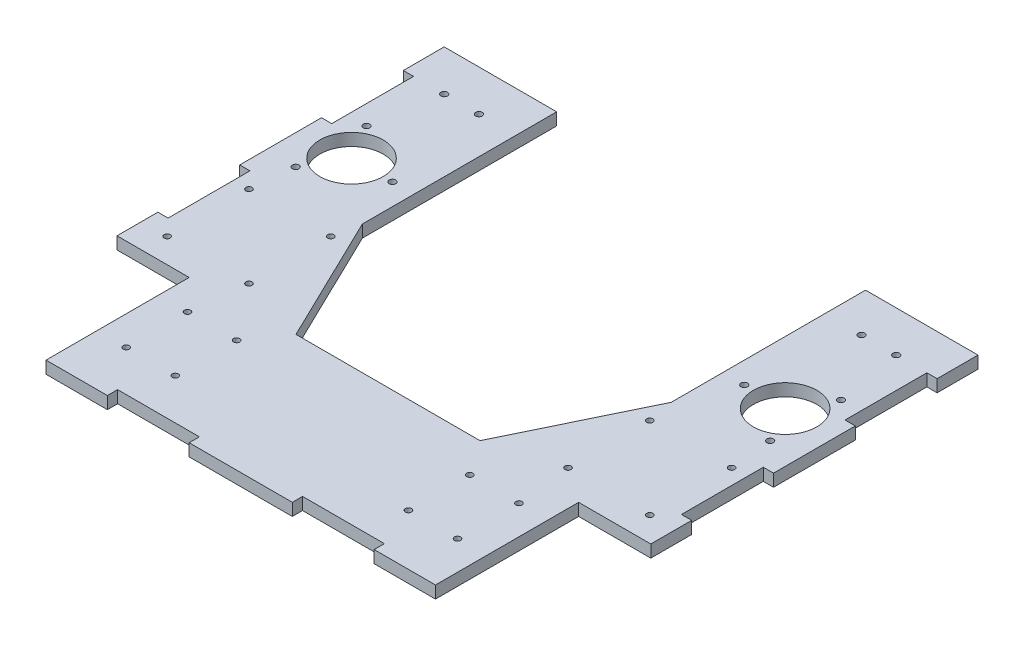
SolidWorks part; units mm, degrees
ref_plane "Front Plane" through (0, 0, 0) normal (0, 0, 1) x (1, 0, 0)
ref_plane "Top Plane" through (0, 0, 0) normal (0, 1, 0) x (1, 0, 0)
ref_plane "Right Plane" through (0, 0, 0) normal (1, 0, 0) x (0, 0, -1)
sketch "Sketch3" plane through (0, 0, 0) normal (0, 1, 0) x (1, 0, 0)
  line L0 (-85.1329, 76.7277) -> (-85.1329, -123.2723)
  line L1 (-85.1329, 76.7277) -> (-30.1329, 76.7277)
  line L2 (-30.1329, 76.7277) -> (-30.1329, 11.7277)
  line L3 (-30.1329, 11.7277) -> (0.3794, -51.2723)
  line L4 (0.3794, -51.2723) -> (90.3794, -51.2723)
  line L5 (-85.1329, -123.2723) -> (175.8917, -123.2723)
  line L6 (45.3794, 120.3098) -> (45.3794, -136.4066) construction
  line L7 (120.8917, 11.7277) -> (90.3794, -51.2723)
  line L8 (120.8917, 76.7277) -> (120.8917, 11.7277)
  line L9 (175.8917, 76.7277) -> (120.8917, 76.7277)
  line L10 (175.8917, 76.7277) -> (175.8917, -123.2723)
  point P11 (45.3794, -123.2723)
  point P12 (45.3794, -51.2723)
  dimension "D1" = 200
  dimension "D2" = 55
  dimension "D3" = 65
  dimension "D4" = 45
  dimension "D5" = 70
  dimension "D6" = 72
  dimension "D7" = 55
  dimension "D8" = 200
  dimension "D9" = 261.0246
  dimension "D10" = 151.0246
extrude "Boss-Extrude1" add sketch "Sketch3" along normal blind 6
sketch "Sketch4" plane through (0, 6, 0) normal (0, 1, 0) x (1, 0, 0)
  line L0 (-54.8456, -88.8518) -> (-54.8456, -98.9429) construction
  line L1 (-85.1329, -123.2723) -> (-49.8456, -123.2723)
  line L2 (-85.1329, -123.2723) -> (-85.1329, -53.2723)
  line L3 (-85.1329, -53.2723) -> (-49.8456, -53.2723)
  line L4 (-49.8456, -123.2723) -> (-49.8456, -53.2723)
  line L5 (45.3794, -51.2723) -> (45.3794, 91.9306) construction
  line L6 (90.3794, -51.2723) -> (0.3794, -51.2723) construction
  line L7 (140.6044, -123.2723) -> (140.6044, -53.2723)
  line L8 (175.8917, -53.2723) -> (140.6044, -53.2723)
  line M8 (-85.1329, -123.2723) -> (175.8917, -123.2723)
  line M9 (175.8917, -123.2723) -> (175.8917, 76.7277)
  dimension "D1" = 5
  dimension "D2" = 70
extrude "Cut-Extrude1" cut sketch "Sketch4" against normal blind 10 contours L8 L7 M9 M8 | L3 L4 L1 L2 region at (158.248, 6, 88.2723)
sketch "Sketch8" plane through (0, 0, -76.7277) normal (0, 0, -1) x (-1, 0, 0)
  line L1 (-175.8917, 6) -> (-120.8917, 6)
  line L2 (-175.8917, 6) -> (-175.8917, 0)
  line L3 (-175.8917, 0) -> (-120.8917, 0)
  line L4 (-120.8917, 6) -> (-120.8917, 0)
  line L5 (30.1329, 6) -> (85.1329, 6)
  line L6 (30.1329, 6) -> (30.1329, 0)
  line L7 (30.1329, 0) -> (85.1329, 0)
  line L8 (85.1329, 6) -> (85.1329, 0)
extrude "Boss-Extrude2" add sketch "Sketch8" along normal blind 30
sketch "Sketch10" plane through (0, 6, 0) normal (0, 1, 0) x (1, 0, 0)
  line L0 (-85.1329, 106.7277) -> (-85.1329, -53.2723) construction
  line L1 (-85.1329, 86.7277) -> (-80.1329, 86.7277)
  line L2 (-85.1329, 86.7277) -> (-85.1329, 46.7277)
  line L3 (-85.1329, 46.7277) -> (-80.1329, 46.7277)
  line L4 (-80.1329, 86.7277) -> (-80.1329, 46.7277)
  line L6 (-85.1329, 6.7277) -> (-80.1329, 6.7277)
  line L7 (-85.1329, 6.7277) -> (-85.1329, -33.2723)
  line L8 (-85.1329, -33.2723) -> (-80.1329, -33.2723)
  line L9 (-80.1329, 6.7277) -> (-80.1329, -33.2723)
  line L10 (-85.1329, 106.7277) -> (-30.1329, 106.7277) construction
  line L11 (-85.1329, -53.2723) -> (-49.8456, -53.2723) construction
  line L12 (45.3794, -51.2723) -> (45.3794, 130.7812) construction
  line L13 (90.3794, -51.2723) -> (0.3794, -51.2723) construction
  line L14 (170.8917, 6.7277) -> (170.8917, -33.2723)
  line L15 (175.8917, -33.2723) -> (170.8917, -33.2723)
  line L16 (175.8917, 6.7277) -> (175.8917, -33.2723)
  line L17 (175.8917, 6.7277) -> (170.8917, 6.7277)
  line L18 (170.8917, 86.7277) -> (170.8917, 46.7277)
  line L19 (175.8917, 46.7277) -> (170.8917, 46.7277)
  line L20 (175.8917, 86.7277) -> (175.8917, 46.7277)
  line L21 (175.8917, 86.7277) -> (170.8917, 86.7277)
  line L22 (-49.8456, -123.2723) -> (140.6044, -123.2723) construction
  line L23 (-19.8456, -123.2723) -> (20.1544, -123.2723)
  line L24 (-19.8456, -123.2723) -> (-19.8456, -118.2723)
  line L25 (-19.8456, -118.2723) -> (20.1544, -118.2723)
  line L26 (20.1544, -123.2723) -> (20.1544, -118.2723)
  line L27 (-49.8456, -123.2723) -> (-49.8456, -53.2723) construction
  line L28 (70.6044, -123.2723) -> (110.6044, -123.2723)
  line L29 (70.6044, -123.2723) -> (70.6044, -118.2723)
  line L30 (70.6044, -118.2723) -> (110.6044, -118.2723)
  line L31 (110.6044, -123.2723) -> (110.6044, -118.2723)
  line L32 (140.6044, -123.2723) -> (140.6044, -53.2723) construction
  point P36 (-19.8456, -120.7723)
  dimension "D1" = 5
  dimension "D2" = 5
  dimension "D3" = 40
  dimension "D4" = 40
  dimension "D5" = 20
  dimension "D6" = 20
  dimension "D7" = 5
  dimension "D8" = 5
  dimension "D9" = 30
  dimension "D10" = 40
  dimension "D11" = 40
  dimension "D12" = 30
extrude "Cut-Extrude2" cut sketch "Sketch10" against normal blind 10
sketch "Sketch11" plane through (0, 0, 0) normal (0, 1, 0) x (1, 0, 0)
  circle A0 centre (-35.6329, -68.2723) radius 1.5
  circle A1 centre (-11.6329, -68.2723) radius 1.5
  circle A2 centre (-11.6329, -98.2723) radius 1.5
  circle A3 centre (-35.6329, -98.2723) radius 1.5
  circle A4 centre (102.3917, -68.2723) radius 1.5
  circle A5 centre (102.3917, -98.2723) radius 1.5
  circle A6 centre (126.3917, -98.2723) radius 1.5
  circle A7 centre (126.3917, -68.2723) radius 1.5
extrude "Cut-Extrude3" cut sketch "Sketch11" along normal blind 10
sketch "Sketch12" plane through (0, 0, 0) normal (0, 1, 0) x (1, 0, 0)
  circle A0 centre (138.8917, 86.7277) radius 1.6
  circle A1 centre (155.8917, 86.7277) radius 1.6
extrude "Cut-Extrude4" cut sketch "Sketch12" along normal blind 27
sketch "Sketch13" plane through (0, 0, 0) normal (0, 1, 0) x (1, 0, 0)
  circle A0 centre (-65.1329, 86.7277) radius 1.6
  circle A1 centre (-48.1329, 86.7277) radius 1.6
extrude "Cut-Extrude5" cut sketch "Sketch13" along normal blind 39
sketch "Sketch14" plane through (0, 0, 0) normal (0, 1, 0) x (1, 0, 0)
  circle A0 centre (-70.6329, 54.2277) radius 1.6
  circle A1 centre (-40.6329, 36.9072) radius 1.6
  circle A3 centre (-70.6329, 19.5867) radius 1.6
  circle A4 centre (-72.6329, -1.2473) radius 1.5
  circle A5 centre (-32.6329, -1.2473) radius 1.5
  circle A6 centre (-32.6329, -41.2473) radius 1.5
  circle A7 centre (-72.6329, -41.2473) radius 1.5
  circle A8 centre (163.3917, -41.2473) radius 1.5
  circle A9 centre (123.3917, -41.2473) radius 1.5
  circle A10 centre (123.3917, -1.2473) radius 1.5
  circle A11 centre (163.3917, -1.2473) radius 1.5
  circle A12 centre (161.3917, 19.5867) radius 1.6
  circle A13 centre (131.3917, 36.9072) radius 1.6
  circle A14 centre (161.3917, 54.2277) radius 1.6
extrude "Cut-Extrude6" cut sketch "Sketch14" along normal blind 10
sketch "Sketch15" plane through (-65.9546, -135.2109, -209.7386) normal (0, 1, 0) x (1, 0, 0)
  circle A0 centre (5.3217, -172.8314) radius 15.5
extrude "Cut-Extrude7" cut sketch "Sketch15" along normal through all and the other way blind 15
sketch "Sketch16" plane through (-65.9546, -135.2109, -209.7386) normal (0, 1, 0) x (1, 0, 0)
  circle A0 centre (217.3463, -172.8314) radius 15.5
extrude "Cut-Extrude8" cut sketch "Sketch16" against normal through all both and the other way through all
